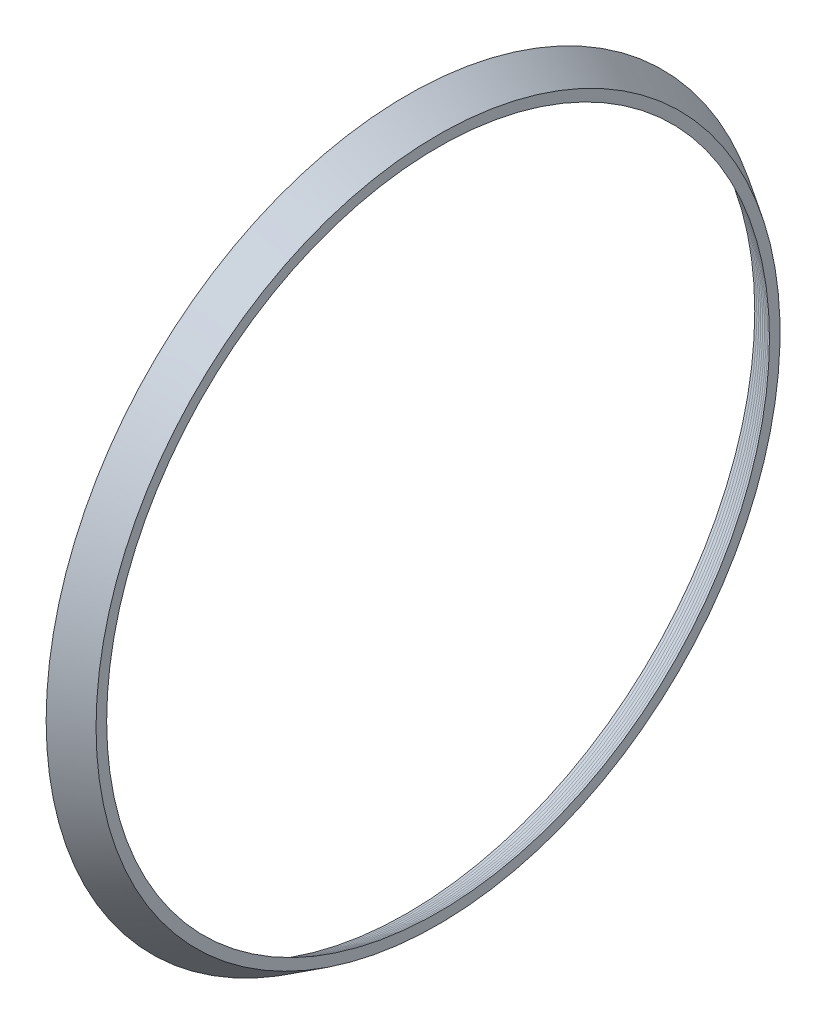
SolidWorks part; units mm, degrees
ref_plane "Front Plane" through (0, 0, 0) normal (0, 0, 1) x (1, 0, 0)
ref_plane "Top Plane" through (0, 0, 0) normal (0, 1, 0) x (1, 0, 0)
ref_plane "Right Plane" through (0, 0, 0) normal (1, 0, 0) x (0, 0, -1)
sketch "Bottle_Liner_Seat Sketch" plane through (0, 0, 0) normal (0, 0, 1) x (1, 0, 0)
  line L0 (-300, 0) -> (300, 0) construction
  line L1 (3.175, 68.3221) -> (2.3812, 68.7898)
  line L2 (2.3812, 68.7898) -> (1.5875, 69.2417)
  line L3 (1.5875, 69.2417) -> (0.7938, 69.6783)
  line L4 (0.7938, 69.6783) -> (0, 70.1)
  line L5 (0, 70.1) -> (-0.7938, 70.5072)
  line L6 (-0.7938, 70.5072) -> (-1.5875, 70.9004)
  line L7 (-1.5875, 70.9004) -> (-2.3812, 71.2799)
  line L8 (-2.3812, 71.2799) -> (-3.175, 71.646)
  line L9 (-3.175, 71.646) -> (-3.175, 74.4485)
  line L10 (-3.175, 74.4485) -> (3.175, 70.5115)
  line L11 (3.175, 70.5115) -> (3.175, 68.3221)
revolve "Bottle_Liner_Seat" add sketch "Bottle_Liner_Seat Sketch" angle 360 about L0
ref_axis "Engine Axis" through (3.4925, 0, 0) along (-1, 0, 0)
